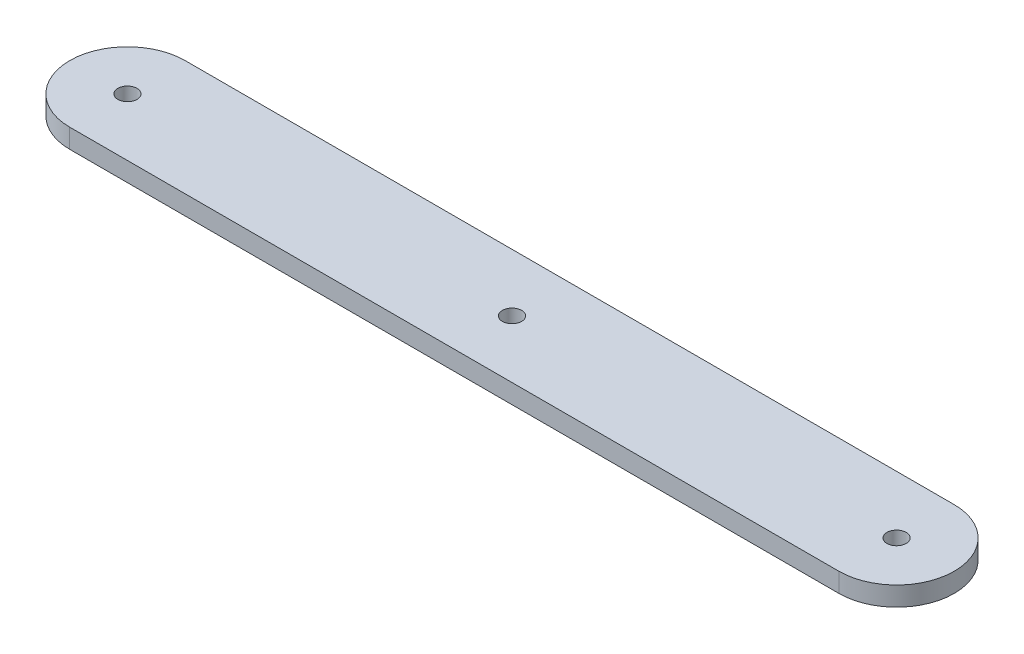
SolidWorks part; units mm, degrees
ref_plane "前视基准面" through (0, 0, 0) normal (0, 0, 1) x (1, 0, 0)
ref_plane "上视基准面" through (0, 0, 0) normal (0, 1, 0) x (1, 0, 0)
ref_plane "右视基准面" through (0, 0, 0) normal (1, 0, 0) x (0, 0, -1)
other "Configuration Table"
sketch "草图1" plane through (0, 0, 0) normal (0, 1, 0) x (1, 0, 0)
  line L0 (0, 0) -> (200, 0) construction
  line L1 (0, 15) -> (200, 15)
  line L2 (0, -15) -> (200, -15)
  arc A0 (0, 15) -> (0, -15) centre (0, 0) ccw
  arc A1 (200, -15) -> (200, 15) centre (200, 0) ccw
  circle A2 centre (200, 0) radius 2.5
  circle A3 centre (100, 0) radius 2.5
  circle A4 centre (0, 0) radius 2.5
  point P3 (100, 0)
  dimension "D2" = 15
  dimension "D3" = 5
  dimension "D4" = 5
  dimension "D5" = 5
  dimension "D1" = 200
extrude "凸台-拉伸1" add sketch "草图1" along normal blind 5
